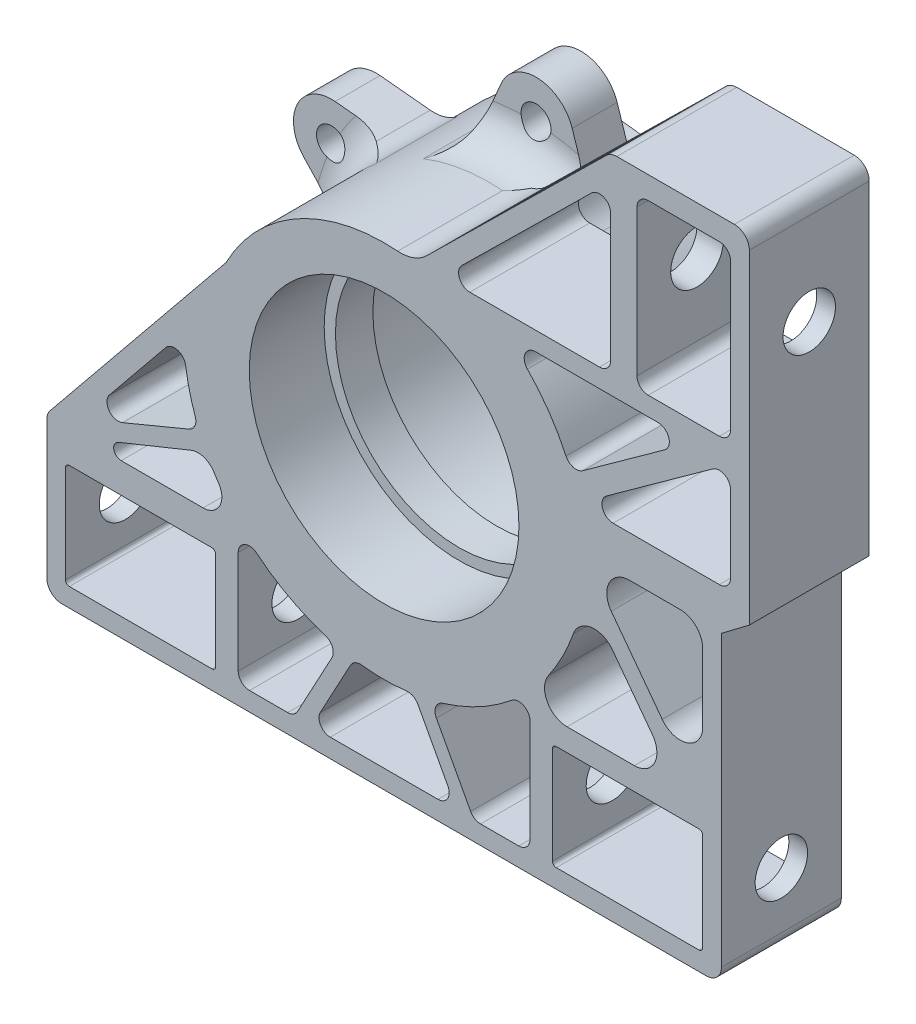
SolidWorks part; units mm, degrees
material "7075-T6 (SN)"
ref_plane "Front Plane" through (0, 0, 0) normal (0, 0, 1) x (1, 0, 0)
ref_plane "Top Plane" through (0, 0, 0) normal (0, 1, 0) x (1, 0, 0)
ref_plane "Right Plane" through (0, 0, 0) normal (1, 0, 0) x (0, 0, -1)
sketch "Sketch1" plane through (0, 0, 0) normal (0, 0, 1) x (1, 0, 0)
  circle A0 centre (0, 0) radius 36
  circle A1 centre (0, 0) radius 47.5
  dimension "D1" = 72
  dimension "D2" = 95
extrude "Boss-Extrude1" add sketch "Sketch1" along normal blind 60
sketch "Sketch2" plane through (0, 0, 0) normal (0, 0, -1) x (-1, 0, 0)
  line L0 (0, 0) -> (0, -79) construction
  line L1 (-86.05, -79) -> (86.05, -79)
  line L2 (90.05, -75) -> (90.05, -38.4217)
  line L4 (-62.1377, 98.5) -> (-93.5, 98.5)
  line L6 (-65, -60) -> (65, -60) construction
  line L7 (-65, -60) -> (-65, 70) construction
  line L8 (-65, 70) -> (-80, 70) construction
  line L9 (-84.05, -74) -> (-45.95, -74)
  line L10 (-85.05, -73) -> (-85.05, -47)
  line L11 (-84.05, -46) -> (-45.95, -46)
  line L12 (-44.95, -73) -> (-44.95, -47)
  line L13 (-85.05, -74) -> (-44.95, -46) construction
  line L14 (-85.05, -46) -> (-44.95, -74) construction
  line L15 (45.95, -74) -> (84.05, -74)
  line L16 (44.95, -73) -> (44.95, -47)
  line L17 (45.95, -46) -> (84.05, -46)
  line L18 (85.05, -73) -> (85.05, -47)
  line L19 (44.95, -74) -> (85.05, -46) construction
  line L20 (44.95, -46) -> (85.05, -74) construction
  line L25 (-97.5, 94.5) -> (-97.5, 7.8481)
  line L26 (-89.5, 92.5) -> (-70.5, 92.5)
  line L27 (-92.5, 89.5) -> (-92.5, 50.5)
  line L28 (-89.5, 47.5) -> (-70.5, 47.5)
  line L29 (-67.5, 89.5) -> (-67.5, 50.5)
  line L30 (-92.5, 92.5) -> (-67.5, 47.5) construction
  line L31 (-92.5, 47.5) -> (-67.5, 92.5) construction
  line L32 (-90.05, -75) -> (-90.05, 2.2122)
  line L33 (-90.05, 2.2122) -> (-97.5, 7.8481)
  line L34 (89.1527, -35.8972) -> (42.19, 21.8232)
  line L35 (-59.3325, 97.3515) -> (-7.9717, 46.8263)
  line L36 (-60.5, 84.5598) -> (-60.5, 50.5)
  line L37 (-57.5, 47.5) -> (-22.8769, 47.5)
  line L38 (-20.7731, 52.6386) -> (-55.3961, 86.6985)
  line L39 (-92.5, 36.6411) -> (-92.5, 16.2085)
  line L40 (-89.5, 13.2085) -> (-61.1399, 13.2085)
  line L41 (-59.3862, 18.6425) -> (-87.7463, 39.0751)
  line L42 (-74.9028, 37.0659) -> (-53.0252, 21.3038)
  line L43 (-73.1491, 42.5) -> (-40.398, 42.5)
  line L44 (-85.05, -3.7878) -> (-85.05, -21.9711)
  line L45 (-74.2465, -25.5665) -> (-60.6364, -7.3832)
  line L46 (-65.4398, 2.2122) -> (-79.05, 2.2122)
  line L47 (-71.6224, -30.4046) -> (-60.9384, -16.1307)
  line L49 (73.3193, -24.3593) -> (58.2889, -5.8859)
  line L50 (69.841, -29.0229) -> (52.1008, -21.6509)
  line L53 (-38.95, -43.5872) -> (-38.95, -71)
  line L57 (38.95, -43.5872) -> (38.95, -71)
  line L60 (-66.8189, -40) -> (-48.8288, -40)
  line L61 (-35.95, -74) -> (-25.7412, -74)
  line L62 (-23.1003, -72.4232) -> (-13.9448, -55.434)
  line L63 (-9.0141, -54.7162) -> (-17.0225, -69.5768)
  line L64 (-14.3816, -74) -> (14.3816, -74)
  line L65 (35.95, -74) -> (25.7412, -74)
  line L66 (23.1003, -72.4232) -> (13.9448, -55.434)
  line L67 (9.0141, -54.7162) -> (17.0225, -69.5768)
  line L69 (51.5556, -26.2603) -> (70.9493, -34.1228)
  line L70 (70.1979, -37.9763) -> (48.3199, -37.9763)
  circle A0 centre (0, 0) radius 47.5 construction
  arc A1 (32.4962, 42.5) -> (-49.9727, 19.1045) centre (0, 0) ccw construction
  arc A2 (-38.253, 37.4027) -> (-48.5491, 22.4774) centre (0, 0) ccw
  arc A3 (-51.8439, 13.2085) -> (-53.4971, 0.5598) centre (0, 0) ccw construction
  arc A4 (-50.4743, -17.7369) -> (-43.9049, -30.5714) centre (0, 0) ccw
  arc A5 (-53.1874, -5.7753) -> (-35.5282, -40) centre (0, 0) ccw construction
  arc A6 (-6.0348, -53.1585) -> (6.0348, -53.1585) centre (0, 0) ccw
  arc A7 (-8.032, -52.8936) -> (8.032, -52.8936) centre (0, 0) ccw construction
  arc A8 (15.7051, -51.1429) -> (34.0412, -41.2729) centre (0, 0) ccw
  arc A9 (12.1493, -52.1022) -> (38.95, -36.6763) centre (0, 0) ccw construction
  arc A10 (50.4245, -17.878) -> (52.9905, -7.3662) centre (0, 0) ccw
  arc A11 (49.4041, -20.5302) -> (53.5, 0) centre (0, 0) ccw construction
  arc A12 (-34.0412, -41.2729) -> (-15.7051, -51.1429) centre (0, 0) ccw
  arc A13 (-38.95, -36.6763) -> (-12.1493, -52.1022) centre (0, 0) ccw construction
  arc A15 (45.4311, -28.2535) -> (44.19, -30.1578) centre (0, 0) cw
  arc A16 (-45.95, -74) -> (-44.95, -73) centre (-45.95, -73) ccw
  arc A17 (-84.05, -74) -> (-85.05, -73) centre (-84.05, -73) cw
  arc A18 (-85.05, -47) -> (-84.05, -46) centre (-84.05, -47) cw
  arc A19 (-45.95, -46) -> (-44.95, -47) centre (-45.95, -47) cw
  arc A20 (45.95, -74) -> (44.95, -73) centre (45.95, -73) cw
  arc A21 (84.05, -74) -> (85.05, -73) centre (84.05, -73) ccw
  arc A22 (84.05, -46) -> (85.05, -47) centre (84.05, -47) cw
  arc A23 (44.95, -47) -> (45.95, -46) centre (45.95, -47) cw
  arc A24 (-70.5, 47.5) -> (-67.5, 50.5) centre (-70.5, 50.5) ccw
  arc A25 (-92.5, 50.5) -> (-89.5, 47.5) centre (-89.5, 50.5) ccw
  arc A26 (-89.5, 92.5) -> (-92.5, 89.5) centre (-89.5, 89.5) ccw
  arc A27 (-70.5, 92.5) -> (-67.5, 89.5) centre (-70.5, 89.5) cw
  arc A28 (-22.8769, 47.5) -> (-20.7731, 52.6386) centre (-22.8769, 50.5) ccw
  arc A29 (-60.5, 50.5) -> (-57.5, 47.5) centre (-57.5, 50.5) ccw
  arc A30 (-60.5, 84.5598) -> (-55.3961, 86.6985) centre (-57.5, 84.5598) cw
  arc A31 (-53.0252, 21.3038) -> (-48.5491, 22.4774) centre (-51.2715, 23.7378) ccw
  arc A32 (-74.9028, 37.0659) -> (-73.1491, 42.5) centre (-73.1491, 39.5) cw
  arc A33 (-40.398, 42.5) -> (-38.253, 37.4027) centre (-40.398, 39.5) cw
  arc A34 (-92.5, 16.2085) -> (-89.5, 13.2085) centre (-89.5, 16.2085) ccw
  arc A35 (-61.1399, 13.2085) -> (-59.3862, 18.6425) centre (-61.1399, 16.2085) ccw
  arc A36 (-92.5, 36.6411) -> (-87.7463, 39.0751) centre (-89.5, 36.6411) cw
  arc A37 (-48.8288, -40) -> (-43.9049, -30.5714) centre (-48.8288, -34) ccw
  arc A38 (-60.9384, -16.1307) -> (-50.4743, -17.7369) centre (-56.1349, -19.7261) cw
  arc A39 (-71.6224, -30.4046) -> (-66.8189, -40) centre (-66.8189, -34) ccw
  arc A40 (-85.05, -21.9711) -> (-74.2465, -25.5665) centre (-79.05, -21.9711) ccw
  arc A41 (-60.6364, -7.3832) -> (-65.4398, 2.2122) centre (-65.4398, -3.7878) ccw
  arc A42 (-85.05, -3.7878) -> (-79.05, 2.2122) centre (-79.05, -3.7878) cw
  arc A43 (-25.7412, -74) -> (-23.1003, -72.4232) centre (-25.7412, -71) ccw
  arc A44 (-38.95, -71) -> (-35.95, -74) centre (-35.95, -71) ccw
  arc A45 (-13.9448, -55.434) -> (-15.7051, -51.1429) centre (-16.5857, -54.0108) ccw
  arc A46 (-34.0412, -41.2729) -> (-38.95, -43.5872) centre (-35.95, -43.5872) ccw
  arc A47 (52.1008, -21.6509) -> (50.4245, -17.878) centre (53.252, -18.8805) cw
  arc A48 (58.2889, -5.8859) -> (52.9905, -7.3662) centre (55.9619, -7.7793) ccw
  arc A49 (73.3193, -24.3593) -> (69.841, -29.0229) centre (70.9922, -26.2526) cw
  arc A53 (25.7412, -74) -> (23.1003, -72.4232) centre (25.7412, -71) cw
  arc A54 (38.95, -71) -> (35.95, -74) centre (35.95, -71) cw
  arc A55 (34.0412, -41.2729) -> (38.95, -43.5872) centre (35.95, -43.5872) cw
  arc A56 (13.9448, -55.434) -> (15.7051, -51.1429) centre (16.5857, -54.0108) cw
  arc A57 (9.0141, -54.7162) -> (6.0348, -53.1585) centre (6.3732, -56.1394) ccw
  arc A58 (-9.0141, -54.7162) -> (-6.0348, -53.1585) centre (-6.3732, -56.1394) cw
  arc A59 (-17.0225, -69.5768) -> (-14.3816, -74) centre (-14.3816, -71) ccw
  arc A60 (17.0225, -69.5768) -> (14.3816, -74) centre (14.3816, -71) cw
  arc A61 (86.05, -79) -> (90.05, -75) centre (86.05, -75) ccw
  arc A62 (-86.05, -79) -> (-90.05, -75) centre (-86.05, -75) cw
  arc A64 (90.05, -38.4217) -> (89.1527, -35.8972) centre (86.05, -38.4217) ccw
  arc A65 (-59.3325, 97.3515) -> (-62.1377, 98.5) centre (-62.1377, 94.5) ccw
  arc A66 (-93.5, 98.5) -> (-97.5, 94.5) centre (-93.5, 94.5) ccw
  arc A67 (44.19, -30.1578) -> (48.3199, -37.9763) centre (48.3199, -32.9763) ccw
  arc A68 (51.5556, -26.2603) -> (45.4311, -28.2535) centre (49.677, -30.894) ccw
  arc A69 (70.9493, -34.1228) -> (70.1979, -37.9763) centre (70.1979, -35.9763) cw
  point P6 (0, -79)
  point P12 (0, -60)
  point P58 (0, -74)
  point P67 (0, -74)
  point P125 (-92.5, 42.5)
  point P136 (-85.05, -40)
  point P139 (-53.4542, 2.2122)
  point P144 (-23.95, -74)
  point P147 (-38.95, -74)
  point P164 (85.05, -40.8653)
  point P165 (37.6836, -37.9763)
  point P173 (23.95, -74)
  point P176 (38.95, -74)
  point P191 (-19.4061, -74)
  point P194 (19.4061, -74)
  point P197 (90.05, -79)
  point P203 (90.05, -37)
  point P206 (-60.5, 98.5)
  point P209 (-97.5, 98.5)
  circle M4 centre (0, 0) radius 47.5
  dimension "D16" = 107
  dimension "D18" = 5
  dimension "D25" = 1
  dimension "D26" = 1
  dimension "D27" = 3
  dimension "D28" = 3
  dimension "D29" = 3
  dimension "D30" = 3
  dimension "D31" = 6
  dimension "D32" = 3
  dimension "D33" = 3
  dimension "D34" = 3
  dimension "D35" = 4
  dimension "D36" = 4
  dimension "D39" = 2
  dimension "D7" = 5
  dimension "D1" = 130
  dimension "D2" = 60
  dimension "D3" = 130
  dimension "D4" = 5
  dimension "D5" = 28
  dimension "D6" = 40.1
  dimension "D8" = 28
  dimension "D9" = 6
  dimension "D10" = 15
  dimension "D11" = 25
  dimension "D12" = 45
  dimension "D13" = 5
  dimension "D14" = 5
  dimension "D15" = 37
  dimension "D17" = 85.7231
  dimension "D19" = 6
  dimension "D20" = 6
  dimension "D21" = 15
  dimension "D22" = 4
  dimension "D23" = 42
  dimension "D24" = 0
  dimension "D37" = 5
  dimension "D38" = 5
extrude "Boss-Extrude2" add sketch "Sketch2" against normal blind 32 contours L4 A66 L25 L33 L32 A62 L1 A61 L2 A64 L34 L35 A65 L67 A60 L64 A59 L63 A58 A6 A57 L66 A56 A8 A55 L57 A54 L65 A53 L49 A49 L50 A47 A10 A48 L44 A42 L46 A41 L45 A40 L39 A36 L41 A35 M4 region at (87.0525, -76.0025, 0)
sketch3d "3DSketch1" plane through (0, 0, 0) normal (0, 0, 1) x (1, 0, 0)
  dimension "D1" = 10
sketch "Sketch3" plane through (0, 0, 50) normal (0, 0, 1) x (1, 0, 0)
  line L0 (2.5568, 57.9118) -> (-52.0538, 25.5091) construction
  line L1 (-24.7485, 41.7105) -> (0, 0) construction
  line L2 (12.2094, 61.0501) -> (17.9336, 43.444)
  line L3 (2.5568, 57.9118) -> (0, 0) construction
  line L4 (-6.7817, 61.8886) -> (-14.0352, 44.8555)
  line L5 (-32.643, 33.8147) -> (-51.0689, 35.6112)
  line L6 (-52.0538, 25.5091) -> (0, 0) construction
  line L7 (-46.7247, 5.0796) -> (-59.4341, 18.5411)
  circle A0 centre (0, 0) radius 57.9682 construction
  circle A1 centre (2.5568, 57.9118) radius 4
  circle A2 centre (-52.0538, 25.5091) radius 4
  circle A3 centre (2.5568, 57.9118) radius 10.15
  circle A4 centre (-52.0538, 25.5091) radius 10.15
  circle A5 centre (0, 0) radius 47
  point P7 (-24.7485, 41.7105)
  dimension "D1" = 48.5
  dimension "D2" = 20.3
  dimension "D3" = 8
  dimension "D6" = 20.3
  dimension "D8" = 16
  dimension "D9" = 94
  dimension "D4" = 63.5
  dimension "D5" = 63.5
  dimension "D7" = 16
extrude "Boss-Extrude3" add sketch "Sketch3" against normal blind 12 contours A5 L5 A4 | A5 A4 A2 | A5 A4 L7 | A5 A3 A1 | A5 A3 L4 | A5 L2 A3 region at (14.7205, 52.133, 50) region at (12.2981, 59.4556, 50) region at (-52.7841, 12.0892, 50) region at (-60.9104, 29.8493, 50)
fillet "Fillet4" radius 10 1 edges at (7.9717, 46.8263, 16)
fillet "Fillet1" radius 10 4 edges at (-47.174, 5.5555, 44) (-33.2944, 33.8782, 44) (17.7313, 44.0664, 44) (-13.7788, 45.4576, 44)
fillet "Fillet2" radius 10 2 edges at (2.0951, 47.4538, 38) (-42.6536, 20.9025, 38)
sketch "Sketch4" plane through (97.5, 0, 0) normal (1, 0, 0) x (0, 0, -1)
  line L0 (-16, 92.5) -> (-16, 47.5) construction
  line L2 (-32, 92.5) -> (0, 92.5) construction
  line L3 (-32, 47.5) -> (0, 47.5) construction
  line L4 (-32, 92.5) -> (0, 92.5)
  line L5 (-32, 47.5) -> (0, 47.5)
  circle A1 centre (-16, 70) radius 7
  point P4 (-16, 70)
  dimension "D1" = 14
extrude "Cut-Extrude1" cut sketch "Sketch4" against normal blind 37 contours L0 A1 | A1 L0 region at (97.5, 70, 13.0291) region at (97.5, 70, 18.9709)
sketch "Sketch5" plane through (90.05, 0, 0) normal (1, 0, 0) x (0, 0, -1)
  line L0 (-32, -74) -> (0, -74) construction
  line L1 (-32, -46) -> (0, -46) construction
  line L2 (-32, -74) -> (0, -74)
  line L3 (-32, -46) -> (0, -46)
  line L4 (-16, -46) -> (-16, -74) construction
  circle A0 centre (-16, -60) radius 7
  dimension "D1" = 14
extrude "Cut-Extrude2" cut sketch "Sketch5" along direction (1, 0, 0) on the side against the normal blind 56 contours L4 A0 | A0 L4 region at (90.05, -60, 13.0291) region at (90.05, -60, 18.9709)
mirror "Mirror1" about plane through (0, 0, 0) normal (1, 0, 0) of "Cut-Extrude2"
ref_plane "Plane1" through (0, 0, 30) normal (0, 0, -1) x (-1, 0, 0)
sketch "Sketch6" plane through (0, 0, 30) normal (0, 0, -1) x (-1, 0, 0)
  circle A0 centre (0, 0) radius 36
  circle A1 centre (0, 0) radius 33
  dimension "D1" = 66
extrude "Boss-Extrude4" add sketch "Sketch6" along normal blind 10
ref_plane "Plane2" through (0, 0, -10) normal (0, 0, -1) x (-1, 0, 0)
mirror "Mirror2" about plane through (0, 0, -10) normal (0, 0, -1) of bodies 110
delete or keep bodies "Body-Delete/Keep 1" type delete bodies bodies 110
move or copy body "Body-Move/Copy1" bodies to move or copy 111 copy no translate (0, 0, 17.2704) parameters "D1"=0, "D2"=0, "D3"=17.2704
move or copy body "Body-Move/Copy2" bodies to move or copy 112 copy no translate (0, 0, 3.7438) parameters "D1"=0, "D2"=0, "D3"=3.7438
